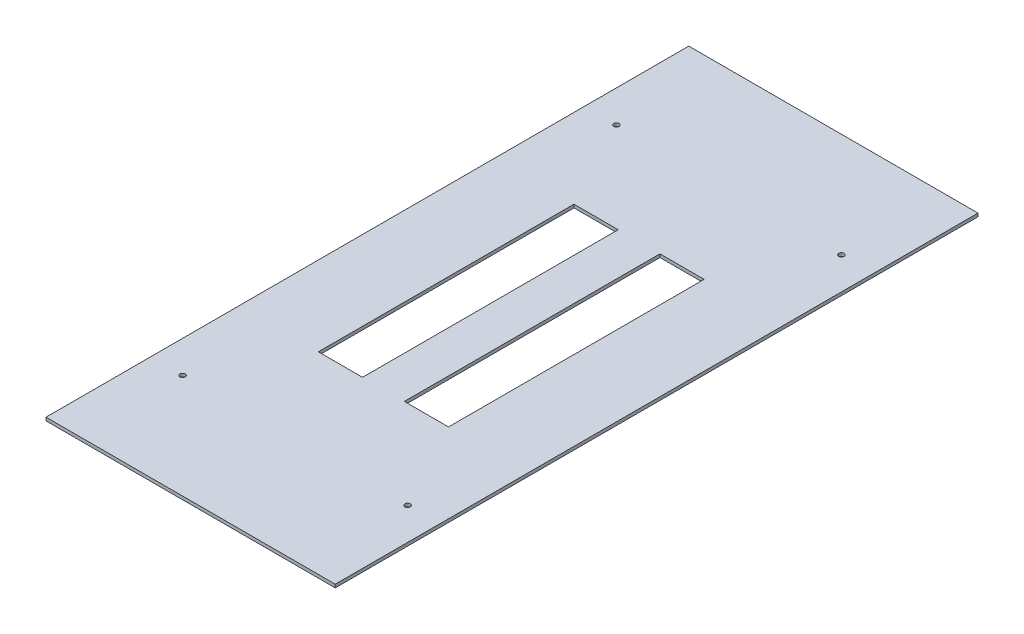
SolidWorks part; units mm, degrees
material "Acrylic (Medium-high impact)"
ref_plane "Front Plane" through (0, 0, 0) normal (0, 0, 1) x (1, 0, 0)
ref_plane "Top Plane" through (0, 0, 0) normal (0, 1, 0) x (1, 0, 0)
ref_plane "Right Plane" through (0, 0, 0) normal (1, 0, 0) x (0, 0, -1)
sketch "Sketch1" plane through (0, 0, 0) normal (0, 1, 0) x (1, 0, 0)
  line L0 (0, 212.5) -> (0, -212.5) construction
  line L1 (-115, 212.5) -> (115, 212.5)
  line L2 (-115, 212.5) -> (-115, -212.5)
  line L3 (-115, -212.5) -> (115, -212.5)
  line L4 (115, 212.5) -> (115, -212.5)
  line L5 (-115, 212.5) -> (115, -212.5) construction
  line L6 (-115, -212.5) -> (115, 212.5) construction
  line L8 (-115, 0) -> (115, 0) construction
  point P0 (0, 0)
  point P8 (-105, 202.5)
  point P14 (105, 202.5)
  point P16 (105, -202.5)
  point P17 (-105, -202.5)
  dimension "D1" = 210
  dimension "D2" = 405
  dimension "D3" = 10
  dimension "D4" = 10
extrude "Boss-Extrude1" add sketch "Sketch1" against normal blind 3 contours L1 L4 L3 L2
hole_wizard "Ø5.0 (4) Diameter Hole1" positions "Sketch2" profile "Sketch4" hole size "Ø5.0" standard "ANSI Metric" end condition through all
sketch "Sketch2" plane through (0, 0, 0) normal (0, 1, 0) x (1, 0, 0)
  point P0 (-105, 202.5)
  point P3 (105, 202.5)
  point P6 (105, -202.5)
  point P9 (-105, -202.5)
sketch "Sketch4" plane through (-105, 0, -202.5) normal (1, 0, 0) x (0, 0, 1)
  line L0 (0, 0) -> (0, 3)
  line L1 (0, 3) -> (2.5, 3)
  line L2 (2.5, 3) -> (2.5, 0)
  line L5 (2.5, 0) -> (0, 0)
  line L11 (0, -6.35) -> (0, 107.95) construction
  dimension "Thru Hole Dia." = 5
  dimension "Thru Hole Depth" = 3
sketch "Sketch5" plane through (0, 0, 0) normal (0, 1, 0) x (1, 0, 0)
  line L0 (0, 212.5) -> (0, -212.5) construction
  line L1 (-55.75, 113.6) -> (-24.5, 113.6) construction
  line L2 (-55.75, 113.6) -> (-55.75, -115) construction
  line L3 (-55.75, -115) -> (-24.5, -115) construction
  line L4 (-24.5, 113.6) -> (-24.5, -115) construction
  line L5 (24.5, 113.6) -> (24.5, -115) construction
  line L6 (-60.75, 118.6) -> (-19.5, 118.6)
  line L7 (-60.75, 118.6) -> (-60.75, -120)
  line L8 (-60.75, -120) -> (-19.5, -120)
  line L9 (-19.5, 118.6) -> (-19.5, -120)
  line L10 (55.75, -115) -> (24.5, -115) construction
  line L11 (55.75, 113.6) -> (55.75, -115) construction
  line L12 (55.75, 113.6) -> (24.5, 113.6) construction
  line L13 (19.5, 118.6) -> (19.5, -120)
  line L14 (60.75, -120) -> (19.5, -120)
  line L15 (60.75, 118.6) -> (60.75, -120)
  line L16 (60.75, 118.6) -> (19.5, 118.6)
  dimension "D1" = 88.9
  dimension "D2" = 228.6
  dimension "D3" = 55.75
  dimension "D4" = 5
  dimension "D5" = 5
  dimension "D6" = 5
  dimension "D7" = 5
  dimension "D8" = 24.5
extrude "Cut-Extrude1" cut sketch "Sketch5" against normal through all
sketch "Sketch6" plane through (0, 0, 0) normal (0, 1, 0) x (1, 0, 0)
  line L1 (-115, -212.5) -> (115, -212.5)
  line L2 (-115, -212.5) -> (-115, 212.5)
  line L3 (-115, 212.5) -> (115, 212.5)
  line L4 (115, -212.5) -> (115, 212.5)
  line L5 (-115, -212.5) -> (115, 212.5) construction
  line L6 (-115, 212.5) -> (115, -212.5) construction
  line L7 (-135, -300) -> (135, -300)
  line L8 (-135, -300) -> (-135, 300)
  line L9 (-135, 300) -> (135, 300)
  line L10 (135, -300) -> (135, 300)
  line L11 (-135, -300) -> (135, 300) construction
  line L12 (-135, 300) -> (135, -300) construction
  point P0 (0, 0)
  point P7 (0, 0)
  dimension "D1" = 270
  dimension "D2" = 600
extrude "Boss-Extrude3" add sketch "Sketch6" against normal up to surface (3 mm away) up to face at (-40.125, -3, 0.7)
